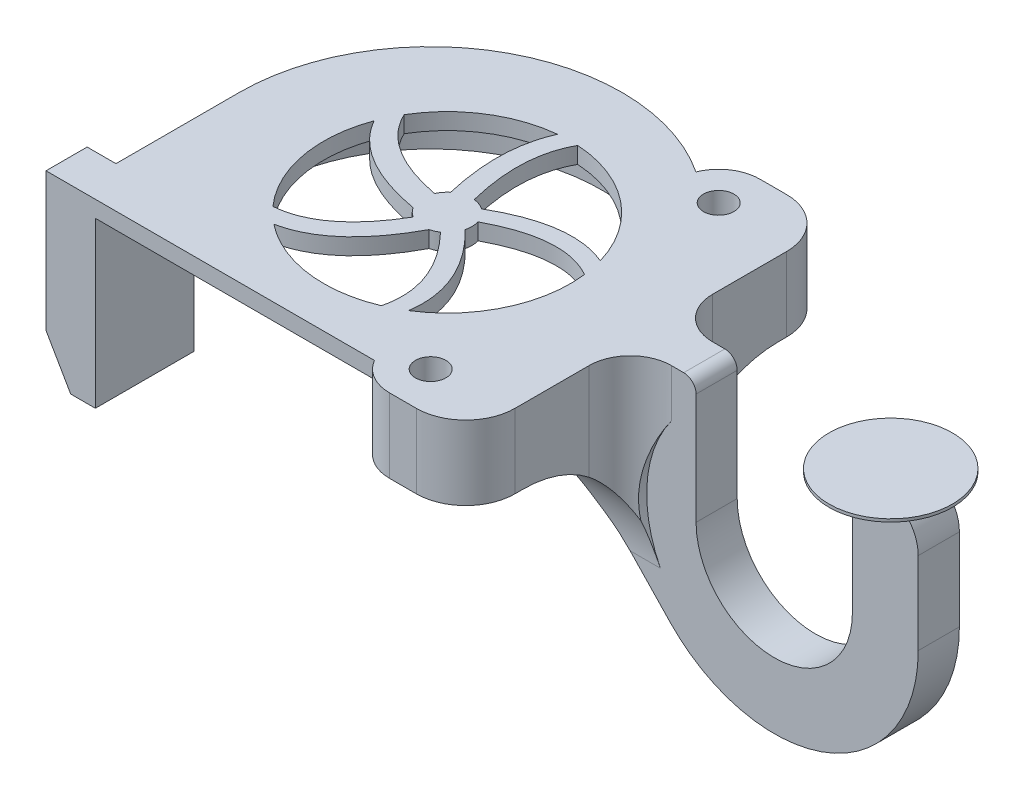
SolidWorks part; units mm, degrees
ref_plane "Front Plane" through (0, 0, 0) normal (0, 0, 1) x (1, 0, 0)
ref_plane "Top Plane" through (0, 0, 0) normal (0, 1, 0) x (1, 0, 0)
ref_plane "Right Plane" through (0, 0, 0) normal (1, 0, 0) x (0, 0, -1)
sketch "Sketch1" plane through (0, 0, 0) normal (0, 1, 0) x (1, 0, 0)
  line L0 (-20.75, 0) -> (-20.75, -20)
  line L1 (18.75, 22.5) -> (26.75, 22.5)
  line L2 (17.5, -22.5) -> (26.75, -22.5)
  line L3 (-23.25, 0) -> (-23.25, -20)
  line L4 (12.5, -17.5) -> (16.0739, -13.1222)
  line L5 (26.75, -22.5) -> (26.75, 22.5)
  line L6 (18.75, 22.5) -> (17.5, 22.5)
  line L7 (-20.75, -20) -> (-23.25, -20)
  arc A2 (-12.8621, 19.3682) -> (-23.25, 0) centre (0, 0) ccw
  arc A3 (16.0739, -13.1222) -> (-20.75, 0) centre (0, 0) ccw
  arc A4 (17.5, 22.5) -> (12.8621, 19.3682) centre (17.5, 17.5) ccw
  arc A5 (12.5, -17.5) -> (17.5, -22.5) centre (17.5, -17.5) ccw
  circle A6 centre (17.5, 17.5) radius 1.85
  circle A8 centre (17.5, -17.5) radius 1.85
  arc A9 (12.8621, 19.3682) -> (-12.8621, 19.3682) centre (0, 0) ccw
  point P19 (0, 23.25)
  dimension "D1" = 41.5
  dimension "D3" = 35
  dimension "D6" = 2.5
  dimension "D7" = 5
  dimension "D8" = 45
  dimension "D2" = 17.5
  dimension "D5" = 3.7
  dimension "D10" = 50
  dimension "D4" = 17.5
  dimension "D12" = 5.75
extrude "Boss-Extrude1" add sketch "Sketch1" along normal blind 9
sketch "Sketch6" plane through (0, 0, 0) normal (0, 0, 1) x (1, 0, 0)
  line L2 (21.25, 9) -> (34.75, 9)
  line L3 (61.75, 9) -> (61.75, -6)
  line L4 (34.75, -6) -> (34.75, 9)
  line L6 (53.75, 9) -> (53.75, -6)
  line L8 (53.75, 9) -> (61.75, 9)
  line L9 (21.25, 9) -> (21.25, -7.2502)
  line L14 (-23.25, 9) -> (-23.25, 0) construction
  line L15 (21.25, -7.2502) -> (31.5916, -18.0837)
  arc A0 (34.75, -6) -> (53.75, -6) centre (44.25, -6) ccw
  arc A1 (31.5916, -18.0837) -> (61.75, -6) centre (44.25, -6) ccw
  dimension "D1" = 8
  dimension "D2" = 19
  dimension "D3" = 15
  dimension "D4" = 67.5
  dimension "D5" = 13.5
extrude "Boss-Extrude4" add sketch "Sketch6" along normal mid plane 5
fillet "Fillet5" radius 5 1 edges at (61.75, 9, 0)
sketch "Sketch9" plane through (0, 9, 0) normal (0, 1, 0) x (1, 0, 0)
  line L0 (-22, 0) -> (-22, -20)
  line L1 (-23.25, -20) -> (-20.75, -20) construction
  line L3 (18.3724, -12.1019) -> (13.1699, -20)
  line L4 (-22, -20) -> (13.1699, -20)
  arc A1 (18.3724, -12.1019) -> (-22, 0) centre (0, 0) ccw
  arc A2 (12.5, -17.5) -> (17.5, -22.5) centre (17.5, -17.5) ccw construction
  circle A3 centre (2, 0) radius 15
extrude "Boss-Extrude5" add sketch "Sketch9" against normal blind 2
sketch "Sketch11" plane through (0, 9, 0) normal (0, 1, 0) x (1, 0, 0)
  line L0 (6.4789, 20.8267) -> (7.3925, 19.0523)
  line L2 (2, 0) -> (2.3017, 2.9848) construction
  line L3 (-13.5533, 10.3271) -> (-11.8686, 11.3972)
  line L4 (19.9538, 1.8879) -> (19.2564, 0.0179)
  line L5 (6.7543, -16.5632) -> (8.749, -16.4967)
  line L6 (-12.6279, -11.6008) -> (-12.8933, -9.6227)
  arc A0 (0.0969, 2.3191) -> (-0.7427, 1.2157) centre (2, 0) ccw
  arc A1 (3.7274, 2.4528) -> (2.3017, 2.9848) centre (2, 0) ccw
  arc A2 (4.9123, -0.7202) -> (4.8722, 0.8664) centre (2, 0) ccw
  arc A3 (2.7138, -2.9138) -> (3.6795, -2.4858) centre (2, 0) ccw
  arc A4 (-0.5507, -1.5793) -> (0.4304, -2.5566) centre (2, 0) ccw
  spline S0 degree 2 poles (2, 0) (-1.0937, 12.6676) (7.55, 16.8997) knots 0 0 0 1 1 1 construction
  spline S2 degree 3 poles (2.3017, 2.9848) (2.177, 3.4869) (1.9866, 4.336) (1.7984, 5.3762) (1.5863, 6.7934) (1.4324, 8.7294) (1.5589, 11.0632) (2.0323, 13.1761) (2.8409, 15.0174) (3.9825, 16.6067) (5.2271, 17.7383) (6.3974, 18.5253) (7.06, 18.8879) (7.3925, 19.0523) knots 0 0 0 0 0.0625 0.103003 0.134253 0.25 0.375 0.5 0.625 0.75 0.875 0.9375 1 1 1 1
  spline S4 degree 3 poles (0.0969, 2.3191) (-0.0325, 2.8699) (-0.2228, 3.7706) (-0.4131, 4.8933) (-0.633, 6.4667) (-0.7847, 8.6614) (-0.6078, 11.3551) (-0.0224, 13.837) (0.9791, 16.0485) (2.3956, 17.9691) (3.9142, 19.3133) (5.3133, 20.2281) (6.0884, 20.6397) (6.4789, 20.8267) knots 0 0 0 0 0.0625 0.099887 0.131137 0.25 0.375 0.5 0.625 0.75 0.875 0.9375 1 1 1 1
  spline S5 degree 3 poles (0.4304, -2.5566) (0.3574, -2.6812) (0.1592, -3.0133) (-0.5111, -4.0842) (-1.653, -5.6551) (-3.2666, -7.346) (-5.0001, -8.6435) (-6.8116, -9.5167) (-8.7123, -9.9819) (-10.3937, -10.0323) (-11.7946, -9.8694) (-12.5338, -9.714) (-12.8933, -9.6227) knots 0.084683 0.084683 0.084683 0.084683 0.103003 0.134253 0.25 0.375 0.5 0.625 0.75 0.875 0.9375 1 1 1 1
  spline S7 degree 3 poles (3.6795, -2.4858) (3.7624, -2.5718) (4.4492, -3.2942) (5.6253, -4.6968) (6.8754, -6.6718) (7.7147, -8.6677) (8.1235, -10.6368) (8.1148, -12.5935) (7.7568, -14.2371) (7.2596, -15.5569) (6.9299, -16.2365) (6.7543, -16.5632) knots 0.118628 0.118628 0.118628 0.118628 0.134253 0.25 0.375 0.5 0.625 0.75 0.875 0.9375 1 1 1 1
  spline S10 degree 3 poles (2.7138, -2.9138) (2.6612, -3.012) (2.4559, -3.3907) (2.1207, -3.9794) (1.3309, -5.2772) (0.1143, -6.9936) (-1.6476, -8.8804) (-3.5836, -10.3632) (-5.6639, -11.3938) (-7.8752, -11.9578) (-9.8132, -12.0334) (-11.4027, -11.8634) (-12.2256, -11.6988) (-12.6279, -11.6008) knots 0.049558 0.049558 0.049558 0.049558 0.0625 0.099887 0.131137 0.25 0.375 0.5 0.625 0.75 0.875 0.9375 1 1 1 1
  spline S11 degree 3 poles (-0.7427, 1.2157) (-0.8845, 1.2427) (-1.2638, 1.318) (-2.4975, 1.5903) (-4.3605, 2.139) (-6.4947, 3.092) (-8.2985, 4.2898) (-9.7287, 5.7035) (-10.8045, 7.338) (-11.4161, 8.9051) (-11.7324, 10.2794) (-11.834, 11.0279) (-11.8686, 11.3972) knots 0.084683 0.084683 0.084683 0.084683 0.103003 0.134253 0.25 0.375 0.5 0.625 0.75 0.875 0.9375 1 1 1 1
  spline S12 degree 3 poles (-0.5507, -1.5793) (-0.6603, -1.5596) (-1.0839, -1.4814) (-1.7473, -1.3445) (-3.2257, -0.9944) (-5.234, -0.3677) (-7.573, 0.7249) (-9.5814, 2.1079) (-11.2044, 3.7679) (-12.4242, 5.6967) (-13.0949, 7.5165) (-13.4244, 9.0807) (-13.5222, 9.9143) (-13.5533, 10.3271) knots 0.049558 0.049558 0.049558 0.049558 0.0625 0.099887 0.131137 0.25 0.375 0.5 0.625 0.75 0.875 0.9375 1 1 1 1
  spline S13 degree 3 poles (3.7274, 2.4528) (3.8368, 2.5163) (4.7772, 3.0537) (6.5587, 3.9277) (9.008, 4.7436) (11.4171, 5.1214) (13.737, 5.033) (15.9491, 4.472) (17.6878, 3.6126) (19.0029, 2.7039) (19.6473, 2.1662) (19.9538, 1.8879) knots 0.115512 0.115512 0.115512 0.115512 0.131137 0.25 0.375 0.5 0.625 0.75 0.875 0.9375 1 1 1 1
  spline S14 degree 3 poles (4.8722, 0.8664) (4.9773, 0.9229) (5.8586, 1.3887) (7.5272, 2.1415) (9.7666, 2.8106) (11.9153, 3.0786) (13.9214, 2.9394) (15.8029, 2.4016) (17.2883, 1.6123) (18.4243, 0.7766) (18.9895, 0.2753) (19.2564, 0.0179) knots 0.118628 0.118628 0.118628 0.118628 0.134253 0.25 0.375 0.5 0.625 0.75 0.875 0.9375 1 1 1 1
  spline S15 degree 3 poles (4.9123, -0.7202) (5.003, -0.8085) (5.7743, -1.5689) (7.0968, -3.0483) (8.5436, -5.1863) (9.5577, -7.404) (10.0989, -9.6616) (10.156, -11.943) (9.7979, -13.8492) (9.278, -15.3608) (8.9342, -16.1264) (8.749, -16.4967) knots 0.115512 0.115512 0.115512 0.115512 0.131137 0.25 0.375 0.5 0.625 0.75 0.875 0.9375 1 1 1 1
  dimension "D1" = 3
  dimension "D3" = 3
extrude "Boss-Extrude6" add sketch "Sketch11" against normal blind 2 contours S15 A2 S14 S10 S13 A1 S2 S4 A0 S11 S12 A4 S5 A3 S7 region at (1.3599, 9, -0.7527)
fillet "Fillet6" radius 1.5 2 edges at (53.75, 9, 0) (34.75, 9, 0)
fillet "Fillet9" radius 13 2 edges at (24, 0, 2.5) (24, 0, -2.5)
fillet "Fillet10" radius 5 2 edges at (26.75, -2, 2.5) (26.75, -2, -2.5)
sketch "Sketch7" plane through (0, 0, -2.5) normal (0, 0, -1) x (-1, 0, 0)
  circle A0 centre (-44.25, -6) radius 15.5
sketch "Sketch8" plane through (0, 0, 2.5) normal (0, 0, 1) x (1, 0, 0)
  circle A0 centre (44.25, -6) radius 15.5
extrude "Cut-Extrude4" cut sketch "Sketch7" along normal blind 5
extrude "Cut-Extrude5" cut sketch "Sketch8" along normal blind 5
fillet "Fillet11" radius 10 1 edges at (21.25, -7.2502, 0)
fillet "Fillet12" radius 6 2 edges at (26.75, 4.5, 22.5) (26.75, 4.5, -22.5)
sketch "Sketch16" plane through (0, 9, 0) normal (0, 1, 0) x (1, 0, 0)
  line L0 (-23.25, -8) -> (-23.25, -15)
  line L1 (-20.75, -20) -> (-26.75, -20)
  line L2 (-20.75, -20) -> (-20.75, -8)
  line L3 (-20.75, -8) -> (-23.25, -8)
  line L4 (-26.75, -20) -> (-26.75, -15)
  line L5 (-23.25, 0) -> (-23.25, -20) construction
  line L6 (-23.25, -15) -> (-26.75, -15)
  dimension "D2" = 12
  dimension "D3" = 5
  dimension "D4" = 3.5
extrude "Boss-Extrude7" add sketch "Sketch16" against normal blind 22
chamfer "Chamfer1" distance 3 angle 60 1 edges at (-26.75, -13, 17.5) first distance on face at (-23.5833, -13, 14.3333)
sketch "Sketch17" plane through (0, 9, 0) normal (0, 1, 0) x (1, 0, 0)
  circle A0 centre (55.9069, 0) radius 7.5
  dimension "D1" = 15
extrude "Boss-Extrude8" add sketch "Sketch17" against normal blind 0.35
